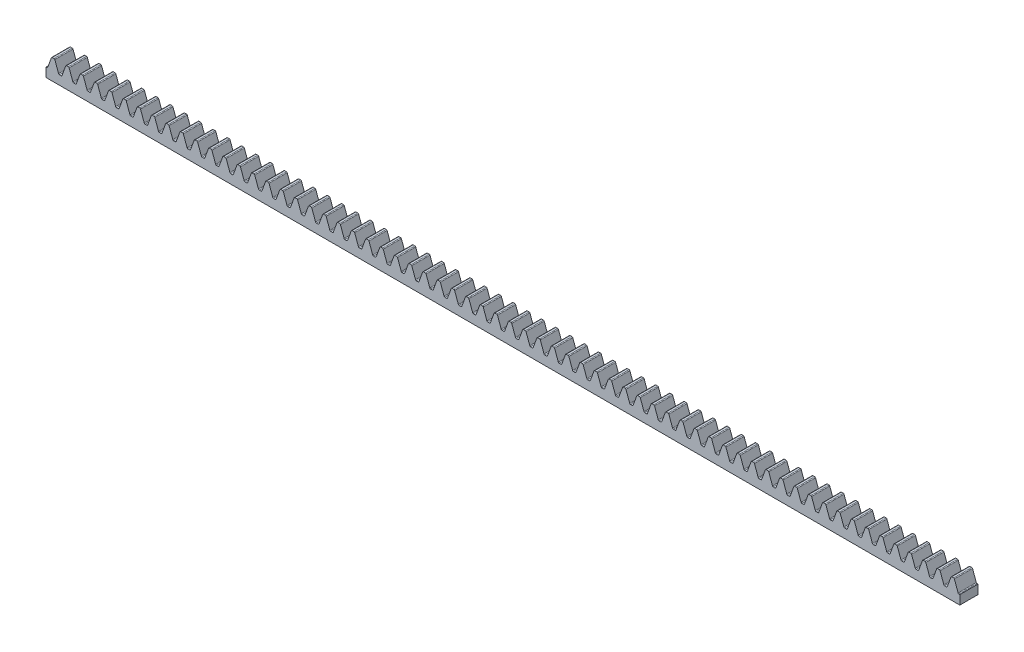
SolidWorks part; units mm, degrees
material "Acrylic (Medium-high impact)"
ref_plane "Front Plane" through (0, 0, 0) normal (0, 0, 1) x (1, 0, 0)
ref_plane "Top Plane" through (0, 0, 0) normal (0, 1, 0) x (1, 0, 0)
ref_plane "Right Plane" through (0, 0, 0) normal (1, 0, 0) x (0, 0, -1)
sketch "Sketch1" plane through (0, 0, 0) normal (0, 0, 1) x (1, 0, 0)
  line L0 (-3.927, 0) -> (3.927, 0)
  line L1 (3.927, 0) -> (3.927, 5)
  line L2 (3.927, 5) -> (3.451, 5)
  line L3 (2.9812, 5.329) -> (0.9458, 10.921)
  line L4 (0.476, 11.25) -> (-0.476, 11.25)
  line L5 (0, -5.5203) -> (0, 27.1646) construction
  line L6 (0, 8.125) -> (1.9635, 8.125) construction
  line L7 (-3.927, 0) -> (-3.927, 5)
  line L8 (-3.927, 5) -> (-3.451, 5)
  line L9 (-2.9812, 5.329) -> (-0.9458, 10.921)
  arc A0 (-0.9458, 10.921) -> (-0.476, 11.25) centre (-0.476, 10.75) cw
  arc A1 (0.9458, 10.921) -> (0.476, 11.25) centre (0.476, 10.75) ccw
  arc A2 (3.451, 5) -> (2.9812, 5.329) centre (3.451, 5.5) cw
  arc A3 (-2.9812, 5.329) -> (-3.451, 5) centre (-3.451, 5.5) cw
  point P13 (0, 0)
  point P16 (0, 11.25)
  point P17 (-0.8261, 11.25)
  point P20 (0.8261, 11.25)
  point P23 (3.1009, 5)
  point P26 (-3.1009, 5)
  dimension "D7" = 0.5
  dimension "D1" = 3.125
  dimension "D2" = 3.125
  dimension "D3" = 110
  dimension "D4" = 5
  dimension "D5" = 3.927
  dimension "D6" = 1.9635
extrude "Boss-Extrude1" add sketch "Sketch1" along normal blind 10
pattern_linear "LPattern2" count 64 spacing 7.854 along (-1, 0, 0) of "Boss-Extrude1"
equation "\"m\"= 2.5'module"
equation "\"phi\"= 20'pressure angle"
equation "\"a\"= 1.25 * \"m\"'addendum"
equation "\"b\"= \"m\"'deddendum"
equation "\"c\"= \"a\" - \"b\"'clearance"
equation "\"pc\"= pi * \"m\"'circular pitch"
equation "\"D1@Sketch1\" = \"b\" + \"c\"'deddendum"
equation "\"D2@Sketch1\" = \"a\"'addendum"
equation "\"D6@Sketch1\" = \"pc\" / 4 "
equation "\"D5@Sketch1\"  = \"pc\" / 2"
equation "\"D7@Sketch1\" = 0.8 * \"c\"'fillet radius"
